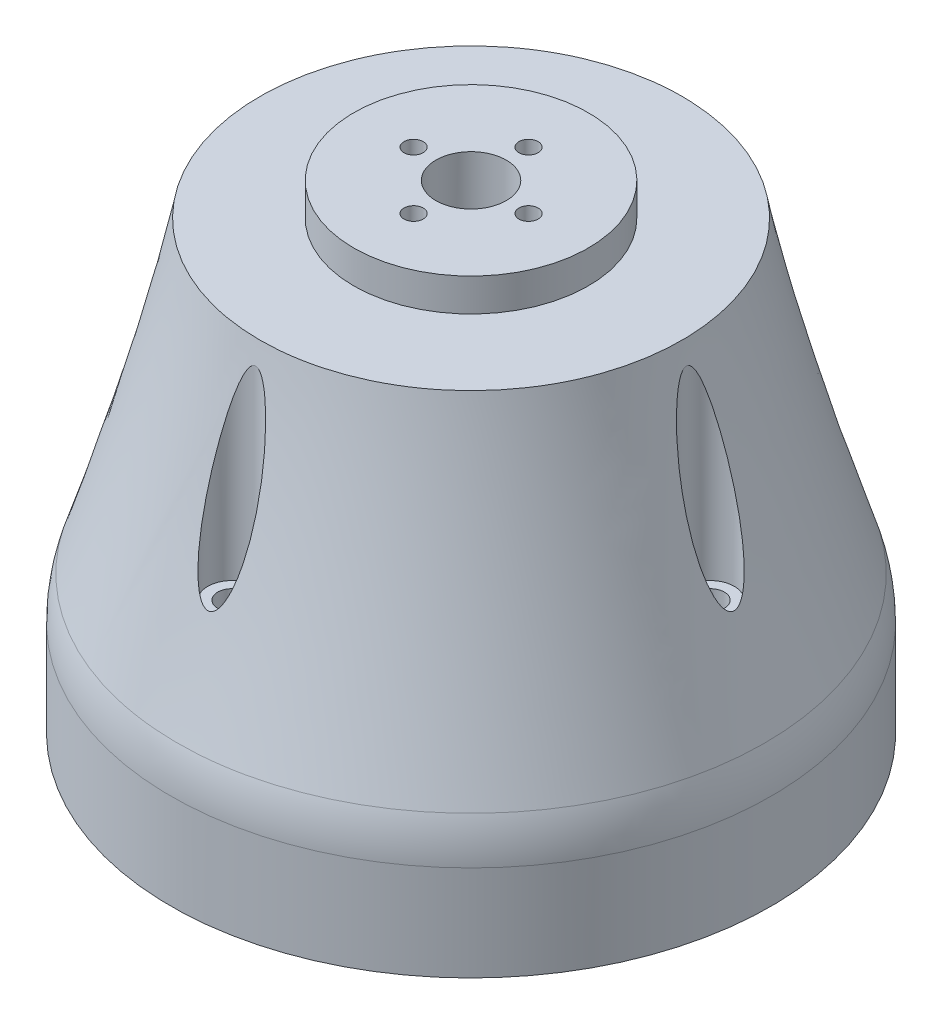
SolidWorks part; units mm, degrees
ref_plane "Front Plane" through (0, 0, 0) normal (0, 0, 1) x (1, 0, 0)
ref_plane "Top Plane" through (0, 0, 0) normal (0, 1, 0) x (1, 0, 0)
ref_plane "Right Plane" through (0, 0, 0) normal (1, 0, 0) x (0, 0, -1)
sketch "Sketch3" plane through (0, 0, 0) normal (0, 1, 0) x (1, 0, 0)
  circle A0 centre (0, 0) radius 64
  dimension "D1" = 128
extrude "Boss-Extrude1" add sketch "Sketch3" along normal blind 15
ref_plane "Plane1" through (0, 85, 0) normal (0, 1, 0) x (1, 0, 0)
sketch "Sketch4" plane through (0, 85, 0) normal (0, 1, 0) x (1, 0, 0)
  circle A0 centre (0, 0) radius 45
  dimension "D1" = 90
sketch "Sketch5" plane through (0, 15, 0) normal (0, 1, 0) x (1, 0, 0)
  circle A1 centre (0, 0) radius 64
  circle A2 centre (0, 0) radius 64
  dimension "D1" = 0
loft "Loft1" add profiles "Sketch5", "Sketch4" connector at (-2.5729, 15, 63.9483) connector at (15.8799, 85, 42.105)
fillet "Fillet1" radius 30 1 edges at (0, 15, 64) type face fillet first side face at (0, 15, 64) second side face at (0, 15, 64)
sketch "Sketch6" plane through (0, 85, 0) normal (0, 1, 0) x (1, 0, 0)
  circle A0 centre (0, 0) radius 51 construction
  circle A1 centre (0, 51) radius 3
  circle A2 centre (51, 0) radius 3
  circle A3 centre (0, -51) radius 3
  circle A4 centre (-51, 0) radius 3
  point P14 (0, 0)
  dimension "D1" = 102
  dimension "D2" = 6
  dimension "D3" = 4
extrude "Cut-Extrude1" cut sketch "Sketch6" against normal blind 85
sketch "Sketch8" plane through (0, 85, 0) normal (0, 1, 0) x (1, 0, 0)
  circle A0 centre (-51, 0) radius 5.11
  circle A1 centre (0, 51) radius 5.11
  circle A2 centre (51, 0) radius 5.11
  circle A3 centre (0, -51) radius 5.11
  point P12 (0, 0)
  dimension "D1" = 10.22
  dimension "D2" = 4
extrude "Cut-Extrude3" cut sketch "Sketch8" against normal blind 45
sketch "Sketch9" plane through (0, 0, 0) normal (0, -1, 0) x (1, 0, 0)
  arc A0 (-16.4684, 53.5238) -> (-53.5238, 16.4684) centre (0, 0) ccw
  arc A1 (-7.1314, 48.6777) -> (7.1314, 48.6777) centre (0, 51) ccw
  arc A5 (-7.1314, 48.6777) -> (-16.4684, 53.5238) centre (-14.2628, 46.3554) ccw
  arc A6 (16.4684, 53.5238) -> (7.1314, 48.6777) centre (14.2628, 46.3554) ccw
  arc A7 (48.6777, 7.1314) -> (53.5238, 16.4684) centre (46.3554, 14.2628) ccw
  arc A8 (48.6777, 7.1314) -> (48.6777, -7.1314) centre (51, 0) ccw
  arc A9 (53.5238, -16.4684) -> (48.6777, -7.1314) centre (46.3554, -14.2628) ccw
  arc A10 (7.1314, -48.6777) -> (16.4684, -53.5238) centre (14.2628, -46.3554) ccw
  arc A11 (7.1314, -48.6777) -> (-7.1314, -48.6777) centre (0, -51) ccw
  arc A12 (-16.4684, -53.5238) -> (-7.1314, -48.6777) centre (-14.2628, -46.3554) ccw
  arc A13 (-48.6777, -7.1314) -> (-53.5238, -16.4684) centre (-46.3554, -14.2628) ccw
  arc A14 (-48.6777, -7.1314) -> (-48.6777, 7.1314) centre (-51, 0) ccw
  arc A15 (-53.5238, 16.4684) -> (-48.6777, 7.1314) centre (-46.3554, 14.2628) ccw
  arc A16 (53.5238, 16.4684) -> (16.4684, 53.5238) centre (0, 0) ccw
  arc A17 (16.4684, -53.5238) -> (53.5238, -16.4684) centre (0, 0) ccw
  arc A18 (-53.5238, -16.4684) -> (-16.4684, -53.5238) centre (0, 0) ccw
  point P15 (0, 0)
  point P35 (0, 0)
  dimension "D1" = 112
  dimension "D2" = 15
  dimension "D3" = 4
  dimension "D4" = 15
  dimension "D5" = 15
extrude "Cut-Extrude4" cut sketch "Sketch9" against normal blind 12
sketch "Sketch17" plane through (0, 12, 0) normal (0, -1, 0) x (1, 0, 0)
  circle A0 centre (0, 0) radius 30
  dimension "D1" = 60
extrude "Cut-Extrude10" cut sketch "Sketch17" against normal blind 69
sketch "Sketch19" plane through (0, 0, 0) normal (0, -1, 0) x (1, 0, 0)
  arc A0 (16.4684, -53.5238) -> (53.5238, -16.4684) centre (0, 0) ccw construction
  circle A1 centre (0, 0) radius 64
  circle A2 centre (0, 0) radius 64
  arc A3 (53.5238, -16.4684) -> (48.6777, -7.1314) centre (46.3554, -14.2628) ccw construction
  arc A4 (48.6777, 7.1314) -> (48.6777, -7.1314) centre (51, 0) ccw construction
  arc A5 (48.6777, 7.1314) -> (53.5238, 16.4684) centre (46.3554, 14.2628) ccw construction
  arc A6 (53.5238, 16.4684) -> (16.4684, 53.5238) centre (0, 0) ccw construction
  arc A7 (-7.1314, 48.6777) -> (7.1314, 48.6777) centre (0, 51) ccw construction
  arc A8 (-7.1314, 48.6777) -> (-16.4684, 53.5238) centre (-14.2628, 46.3554) ccw construction
  arc A9 (16.4684, -53.5238) -> (53.5238, -16.4684) centre (0, 0) ccw
  arc A10 (53.5238, -16.4684) -> (48.6777, -7.1314) centre (46.3554, -14.2628) ccw
  arc A11 (48.6777, 7.1314) -> (48.6777, -7.1314) centre (51, 0) ccw
  arc A12 (48.6777, 7.1314) -> (53.5238, 16.4684) centre (46.3554, 14.2628) ccw
  arc A13 (53.5238, 16.4684) -> (16.4684, 53.5238) centre (0, 0) ccw
  arc A14 (-7.1314, 48.6777) -> (7.1314, 48.6777) centre (0, 51) ccw
  arc A15 (-7.1314, 48.6777) -> (-16.4684, 53.5238) centre (-14.2628, 46.3554) ccw
  arc A18 (16.4684, 53.5238) -> (7.1314, 48.6777) centre (14.2628, 46.3554) ccw
  arc A19 (-7.1314, 48.6777) -> (7.1314, 48.6777) centre (0, 51) ccw
  arc A20 (-7.1314, 48.6777) -> (-16.4684, 53.5238) centre (-14.2628, 46.3554) ccw
  arc A21 (-16.4684, 53.5238) -> (-53.5238, 16.4684) centre (0, 0) ccw
  arc A22 (-53.5238, 16.4684) -> (-48.6777, 7.1314) centre (-46.3554, 14.2628) ccw
  arc A23 (-48.6777, -7.1314) -> (-48.6777, 7.1314) centre (-51, 0) ccw
  arc A24 (-48.6777, -7.1314) -> (-53.5238, -16.4684) centre (-46.3554, -14.2628) ccw
  arc A25 (-53.5238, -16.4684) -> (-16.4684, -53.5238) centre (0, 0) ccw
  arc A26 (-16.4684, -53.5238) -> (-7.1314, -48.6777) centre (-14.2628, -46.3554) ccw
  arc A27 (7.1314, -48.6777) -> (-7.1314, -48.6777) centre (0, -51) ccw
  arc A28 (7.1314, -48.6777) -> (16.4684, -53.5238) centre (14.2628, -46.3554) ccw
  arc A29 (16.4684, -53.5238) -> (53.5238, -16.4684) centre (0, 0) ccw
  arc A30 (53.5238, -16.4684) -> (48.6777, -7.1314) centre (46.3554, -14.2628) ccw
  arc A31 (48.6777, 7.1314) -> (48.6777, -7.1314) centre (51, 0) ccw
  arc A32 (48.6777, 7.1314) -> (53.5238, 16.4684) centre (46.3554, 14.2628) ccw
  arc A33 (53.5238, 16.4684) -> (16.4684, 53.5238) centre (0, 0) ccw
  arc A34 (16.4684, 53.5238) -> (7.1314, 48.6777) centre (14.2628, 46.3554) ccw
  arc A35 (-7.1314, 48.6777) -> (7.1314, 48.6777) centre (0, 51) ccw
  arc A36 (-7.1314, 48.6777) -> (-16.4684, 53.5238) centre (-14.2628, 46.3554) ccw
  arc A37 (-16.4684, 53.5238) -> (-53.5238, 16.4684) centre (0, 0) ccw
  arc A38 (-53.5238, 16.4684) -> (-48.6777, 7.1314) centre (-46.3554, 14.2628) ccw
  arc A39 (-48.6777, -7.1314) -> (-48.6777, 7.1314) centre (-51, 0) ccw
  arc A40 (-48.6777, -7.1314) -> (-53.5238, -16.4684) centre (-46.3554, -14.2628) ccw
  arc A41 (-53.5238, -16.4684) -> (-16.4684, -53.5238) centre (0, 0) ccw
  arc A42 (-16.4684, -53.5238) -> (-7.1314, -48.6777) centre (-14.2628, -46.3554) ccw
  arc A43 (7.1314, -48.6777) -> (-7.1314, -48.6777) centre (0, -51) ccw
  arc A44 (7.1314, -48.6777) -> (16.4684, -53.5238) centre (14.2628, -46.3554) ccw
  arc A45 (16.4684, -53.5238) -> (53.5238, -16.4684) centre (0, 0) ccw
  arc A46 (53.5238, -16.4684) -> (48.6777, -7.1314) centre (46.3554, -14.2628) ccw
  arc A47 (48.6777, 7.1314) -> (48.6777, -7.1314) centre (51, 0) ccw
  arc A48 (48.6777, 7.1314) -> (53.5238, 16.4684) centre (46.3554, 14.2628) ccw
  arc A49 (53.5238, 16.4684) -> (16.4684, 53.5238) centre (0, 0) ccw
  circle M19 centre (0, -51) radius 3
  circle M20 centre (51, 0) radius 3
  circle M21 centre (0, 51) radius 3
  circle M22 centre (-51, 0) radius 3
  circle M23 centre (0, 0) radius 64
  arc M24 (-7.1314, 48.6777) -> (7.1314, 48.6777) centre (0, 51) ccw
  arc M25 (7.1314, 48.6777) -> (16.4684, 53.5238) centre (14.2628, 46.3554) cw
  arc M26 (16.4684, 53.5238) -> (53.5238, 16.4684) centre (0, 0) cw
  arc M27 (53.5238, 16.4684) -> (48.6777, 7.1314) centre (46.3554, 14.2628) cw
  arc M28 (48.6777, 7.1314) -> (48.6777, -7.1314) centre (51, 0) ccw
  arc M29 (48.6777, -7.1314) -> (53.5238, -16.4684) centre (46.3554, -14.2628) cw
  arc M30 (53.5238, -16.4684) -> (16.4684, -53.5238) centre (0, 0) cw
  arc M31 (16.4684, -53.5238) -> (7.1314, -48.6777) centre (14.2628, -46.3554) cw
  arc M32 (7.1314, -48.6777) -> (-7.1314, -48.6777) centre (0, -51) ccw
  arc M33 (-7.1314, -48.6777) -> (-16.4684, -53.5238) centre (-14.2628, -46.3554) cw
  arc M34 (-16.4684, -53.5238) -> (-53.5238, -16.4684) centre (0, 0) cw
  arc M35 (-53.5238, -16.4684) -> (-48.6777, -7.1314) centre (-46.3554, -14.2628) cw
  arc M36 (-48.6777, -7.1314) -> (-48.6777, 7.1314) centre (-51, 0) ccw
  arc M37 (-48.6777, 7.1314) -> (-53.5238, 16.4684) centre (-46.3554, 14.2628) cw
  arc M38 (-53.5238, 16.4684) -> (-16.4684, 53.5238) centre (0, 0) cw
  arc M39 (-16.4684, 53.5238) -> (-7.1314, 48.6777) centre (-14.2628, 46.3554) cw
  dimension "D1" = 0
  dimension "D2" = 0
extrude "Boss-Extrude3" add sketch "Sketch19" along normal blind 10 contours M23 M20 M22 M39 M24 M25 M26 M27 M28 M29 M30 M31 M32 M33 M34 M35 M36 M37 M38 M21 M19 region at (-62.1898, 0, 0)
sketch "Sketch21" plane through (0, 85, 0) normal (0, 1, 0) x (1, 0, 0)
  circle A0 centre (0, 0) radius 25
  dimension "D1" = 50
extrude "Boss-Extrude4" add sketch "Sketch21" along normal blind 7
sketch "Sketch20" plane through (0, 92, 0) normal (0, 1, 0) x (1, 0, 0)
  circle A0 centre (0, 0) radius 12.25 construction
  circle A1 centre (0, 0) radius 7.5
  circle A2 centre (0, 12.25) radius 2.05
  circle A3 centre (12.25, 0) radius 2.05
  circle A4 centre (0, -12.25) radius 2.05
  circle A5 centre (-12.25, 0) radius 2.05
  point P15 (0, 0)
  dimension "D1" = 24.5
  dimension "D2" = 15
  dimension "D3" = 4.1
  dimension "D4" = 4
extrude "Cut-Extrude11" cut sketch "Sketch20" against normal up to surface (11 mm away) up to face at (0, 81, -30)
